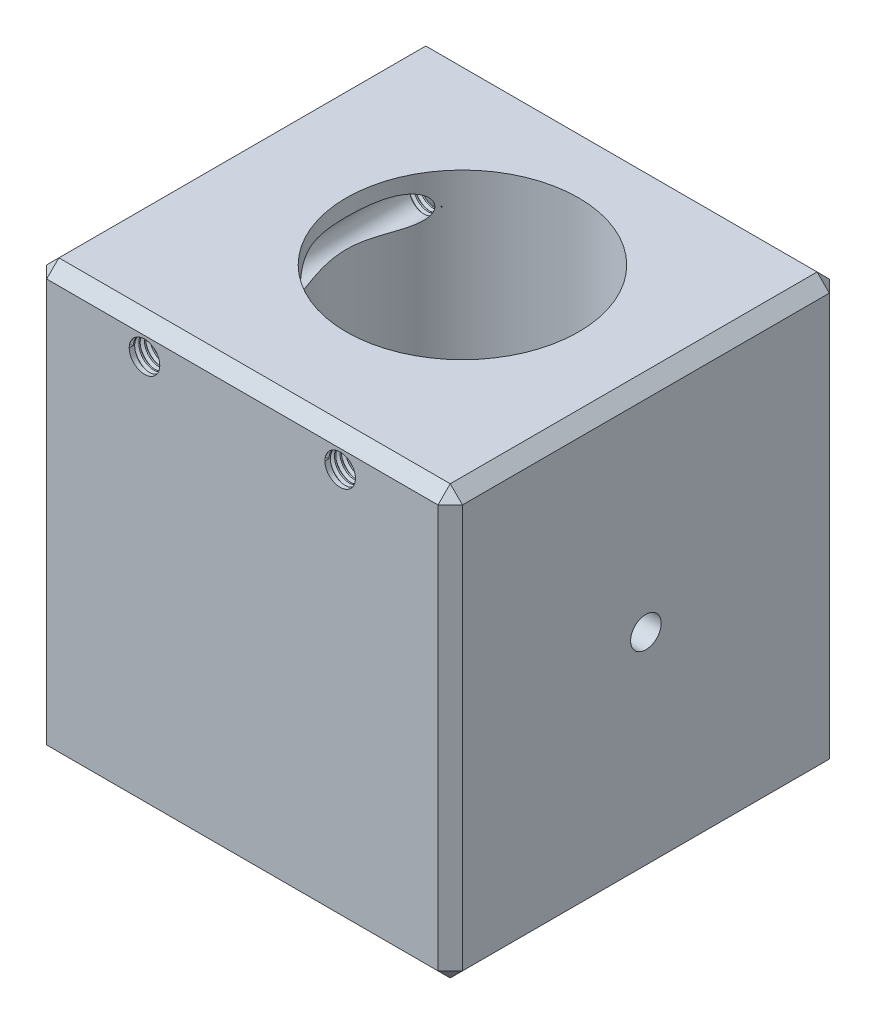
SolidWorks part; units mm, degrees
ref_plane "Front Plane" through (0, 0, 0) normal (0, 0, 1) x (1, 0, 0)
ref_plane "Top Plane" through (0, 0, 0) normal (0, 1, 0) x (1, 0, 0)
ref_plane "Right Plane" through (0, 0, 0) normal (1, 0, 0) x (0, 0, -1)
sketch "Sketch1" plane through (0, 0, 0) normal (0, 1, 0) x (1, 0, 0)
  line L1 (0, 0) -> (34, 0)
  line L2 (0, 0) -> (0, 32)
  line L3 (0, 32) -> (34, 32)
  line L4 (34, 0) -> (34, 32)
  dimension "D1" = 34
  dimension "D2" = 32
extrude "Boss-Extrude1" add sketch "Sketch1" along normal blind 35
sketch "Sketch3" plane through (0, 0, 0) normal (0, -1, 0) x (-1, 0, 0)
  line L1 (-34, 0) -> (-34, 32) construction
  line L2 (0, 0) -> (-34, 0) construction
  circle A0 centre (-18, 17) radius 9.5
  dimension "D1" = 19
  dimension "D2" = 16
  dimension "D3" = 17
extrude "Cut-Extrude1" cut sketch "Sketch3" against normal blind 46
sketch "Sketch4" plane through (34, 0, -2) normal (-1, 0, 0) x (0, 0, 1)
  line L2 (-30, 35) -> (-30, 0) construction
  line L3 (2, 35) -> (-30, 35) construction
  circle A0 centre (-14, 17.5) radius 1.25
  dimension "D3" = 2.5
  dimension "D1" = 17.5
  dimension "D2" = 16
extrude "Cut-Extrude2" cut sketch "Sketch4" along normal blind 9
sketch "Sketch6" plane through (0, 0, 0) normal (0, 0, 1) x (1, 0, 0)
  line L0 (0, 35) -> (34, 35) construction
  line L1 (0, 35) -> (0, 0) construction
  circle A0 centre (9, 32.5) radius 1.25
  circle A1 centre (25, 32.5) radius 1.25
  dimension "D3" = 2.5
  dimension "D4" = 2.5
  dimension "D1" = 2.5
  dimension "D2" = 9
  dimension "D5" = 16
  dimension "D6" = 2.5
extrude "Cut-Extrude3" cut sketch "Sketch6" against normal blind 10
thread "Thread1" pitch 0.45 method cut profile "Thread Profile1" start angle 0, offset 0, length 9, pitch 0.45, diameter 2.5
ref_plane "Plane1" through (23.75, 32.5, 0) normal (0, -1, 0) x (-1, 0, 0)
sketch "Thread Profile1" plane through (23.75, 32.5, 0) normal (0, -1, 0) x (-1, 0, 0)
  line L0 (0, 0) -> (0, 0.45) construction
  line L1 (0, 0) -> (0.2436, 0.1406)
  line L2 (0.2436, 0.1406) -> (0.2436, 0.1969)
  line L3 (0.2436, 0.1969) -> (0, 0.3375)
  line L4 (0.2436, 0.1687) -> (0, 0.1687) construction
  line L11 (0, 0) -> (0, 0.3375)
  point P2 (0, 0)
  dimension "Pitch" = 0.45
  dimension "Profile_Angle" = 60
  dimension "Profile_Land" = 0.0562
  dimension "Profile_Height" = 0.2436
thread "Thread2" pitch 0.45 method cut profile "Thread Profile2" start angle 0, offset 0, length 9, pitch 0.45, diameter 2.5
ref_plane "Plane2" through (7.75, 32.5, 0) normal (0, -1, 0) x (-1, 0, 0)
sketch "Thread Profile2" plane through (7.75, 32.5, 0) normal (0, -1, 0) x (-1, 0, 0)
  line L0 (0, 0) -> (0, 0.45) construction
  line L1 (0, 0) -> (0.2436, 0.1406)
  line L2 (0.2436, 0.1406) -> (0.2436, 0.1969)
  line L3 (0.2436, 0.1969) -> (0, 0.3375)
  line L4 (0.2436, 0.1687) -> (0, 0.1687) construction
  line L11 (0, 0) -> (0, 0.3375)
  point P2 (0, 0)
  dimension "Pitch" = 0.45
  dimension "Profile_Angle" = 60
  dimension "Profile_Land" = 0.0562
  dimension "Profile_Height" = 0.2436
sketch "Sketch17" plane through (0, 0, -32) normal (0, 0, -1) x (-1, 0, 0)
  line L0 (-34, 35) -> (0, 35) construction
  line L1 (-34, 35) -> (-34, 0) construction
  circle A0 centre (-25, 32.5) radius 1.25
  circle A1 centre (-9, 32.5) radius 1.25
  dimension "D1" = 2.5
  dimension "D4" = 2.5
  dimension "D2" = 2.5
  dimension "D3" = 2.5
  dimension "D5" = 16
  dimension "D6" = 9
extrude "Cut-Extrude4" cut sketch "Sketch17" against normal up to surface (32 mm away) up to face at (10.25, 32.5, 0)
thread "Thread3" pitch 0.45 method cut profile "Thread Profile3" start angle 0, offset 0, length 9, pitch 0.45, diameter 2.5
ref_plane "Plane3" through (10.25, 32.5, -32) normal (0, -1, 0) x (1, 0, 0)
sketch "Thread Profile3" plane through (10.25, 32.5, -32) normal (0, -1, 0) x (1, 0, 0)
  line L0 (0, 0) -> (0, 0.45) construction
  line L1 (0, 0) -> (0.2436, 0.1406)
  line L2 (0.2436, 0.1406) -> (0.2436, 0.1969)
  line L3 (0.2436, 0.1969) -> (0, 0.3375)
  line L4 (0.2436, 0.1687) -> (0, 0.1687) construction
  line L11 (0, 0) -> (0, 0.3375)
  point P2 (0, 0)
  dimension "Pitch" = 0.45
  dimension "Profile_Angle" = 60
  dimension "Profile_Land" = 0.0562
  dimension "Profile_Height" = 0.2436
thread "Thread4" pitch 0.45 method cut profile "Thread Profile4" start angle 0, offset 0, length 9, pitch 0.45, diameter 2.5
ref_plane "Plane4" through (26.25, 32.5, -32) normal (0, -1, 0) x (1, 0, 0)
sketch "Thread Profile4" plane through (26.25, 32.5, -32) normal (0, -1, 0) x (1, 0, 0)
  line L0 (0, 0) -> (0, 0.45) construction
  line L1 (0, 0) -> (0.2436, 0.1406)
  line L2 (0.2436, 0.1406) -> (0.2436, 0.1969)
  line L3 (0.2436, 0.1969) -> (0, 0.3375)
  line L4 (0.2436, 0.1687) -> (0, 0.1687) construction
  line L11 (0, 0) -> (0, 0.3375)
  point P2 (0, 0)
  dimension "Pitch" = 0.45
  dimension "Profile_Angle" = 60
  dimension "Profile_Land" = 0.0562
  dimension "Profile_Height" = 0.2436
chamfer "Chamfer1" distance 1 angle 45 12 edges at (0, 0, -16) (17, 0, -32) (34, 0, -16) (17, 0, 0) (0, 17.5, -32) (34, 17.5, -32) (34, 35, -16) (17, 35, -32) (0, 35, -16) (0, 17.5, 0) (17, 35, 0) (34, 17.5, 0)
